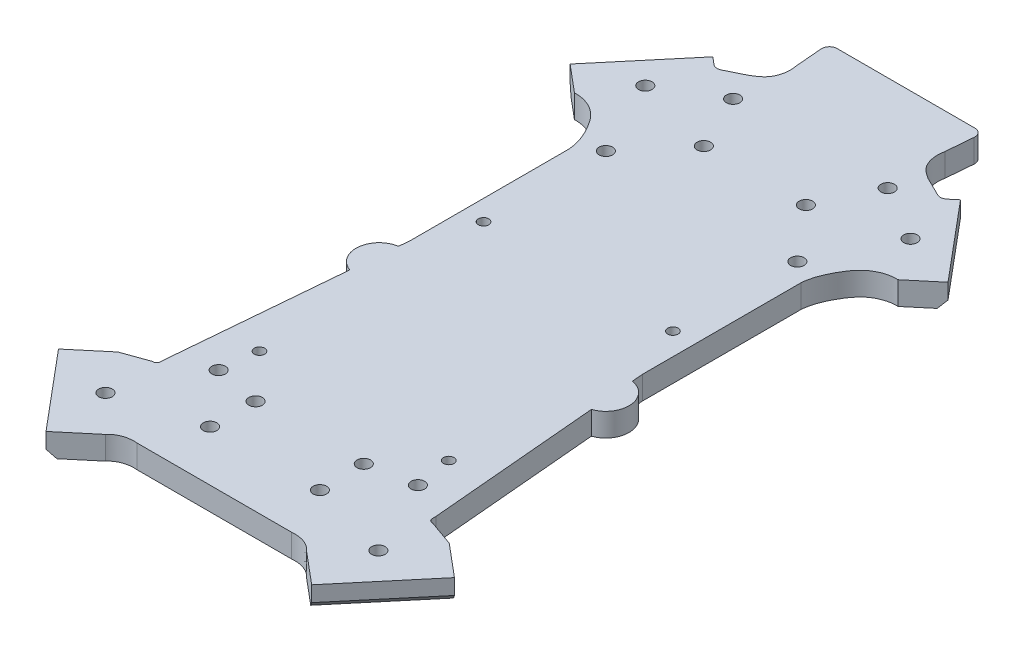
SolidWorks part; units mm, degrees
ref_plane "Front Plane" through (0, 0, 0) normal (0, 0, 1) x (1, 0, 0)
ref_plane "Top Plane" through (0, 0, 0) normal (0, 1, 0) x (1, 0, 0)
ref_plane "Right Plane" through (0, 0, 0) normal (1, 0, 0) x (0, 0, -1)
sketch "Sketch1" plane through (0, 0, 0) normal (0, 1, 0) x (1, 0, 0)
  line L1 (0, 0) -> (200, 0)
  line L2 (0, 0) -> (0, 200)
  line L3 (0, 200) -> (200, 200)
  line L4 (200, 0) -> (200, 200)
  dimension "D1" = 200
  dimension "D2" = 200
extrude "Boss-Extrude1" add sketch "Sketch1" along normal blind 6
sketch "Sketch2" plane through (0, 0, 0) normal (0, -1, 0) x (1, 0, 0)
  line L0 (143.2063, -38.4743) -> (139.3486, -82.5678)
  line L2 (138.3335, -94.1709) -> (138.0819, -97.0459)
  line L3 (138.0819, -97.0459) -> (138.0819, -138.1223)
  line L5 (128.0819, -16.2435) -> (88.0819, -16.2435)
  line L8 (72.9576, -38.4743) -> (76.8153, -82.5678)
  line L10 (77.8304, -94.1709) -> (78.0819, -97.0459)
  line L11 (78.0819, -97.0459) -> (78.0819, -138.1223)
  line L12 (136.0689, -175.4633) -> (131.2216, -177.8581)
  line L14 (127.295, -186.0703) -> (127.8892, -193.0744)
  line L15 (125.8964, -195.2435) -> (90.2675, -195.2435)
  line L16 (108.0819, -195.2435) -> (108.0819, -160.9159) construction
  line L17 (88.8688, -186.0703) -> (88.2746, -193.0744)
  line L18 (80.095, -175.4633) -> (84.9422, -177.8581)
  line L21 (71.8743, -36.5483) -> (65.2141, -34.1729)
  line L22 (65.2141, -34.1729) -> (56.8447, -27.1502)
  line L23 (56.8447, -27.1502) -> (73.7024, -7.0599)
  line L25 (73.7024, -7.0599) -> (82.0719, -14.0827)
  line L30 (66.2141, -151.3141) -> (63.7367, -153.3929)
  line L32 (63.7367, -153.3929) -> (59.1776, -157.2184)
  line L33 (59.1776, -157.2184) -> (76.0353, -177.3087)
  line L35 (76.0353, -177.3087) -> (77.9235, -175.7243)
  line L37 (142.4614, -7.0599) -> (134.092, -14.0827)
  line L38 (159.3191, -27.1502) -> (142.4614, -7.0599)
  line L39 (150.9497, -34.1729) -> (159.3191, -27.1502)
  line L40 (144.2896, -36.5483) -> (150.9497, -34.1729)
  line L45 (149.9497, -151.3141) -> (152.4271, -153.3929)
  line L46 (152.4271, -153.3929) -> (156.9863, -157.2184)
  line L47 (156.9863, -157.2184) -> (140.1285, -177.3087)
  line L48 (140.1285, -177.3087) -> (138.2403, -175.7243)
  line L49 (0, 0) -> (0, -200)
  line L50 (200, 0) -> (0, 0)
  line L51 (200, -200) -> (200, 0)
  line L52 (0, -200) -> (200, -200)
  arc A0 (138.3335, -94.1709) -> (139.3486, -82.5678) centre (137.4028, -88.2435) ccw
  arc A1 (76.8153, -82.5678) -> (77.8304, -94.1709) centre (78.761, -88.2435) ccw
  arc A2 (90.2675, -195.2435) -> (88.2746, -193.0744) centre (90.2675, -193.2435) cw
  arc A3 (127.8892, -193.0744) -> (125.8964, -195.2435) centre (125.8964, -193.2435) cw
  arc A4 (136.0689, -175.4633) -> (138.2403, -175.7243) centre (136.9547, -177.2564) cw
  arc A5 (80.095, -175.4633) -> (77.9235, -175.7243) centre (79.2091, -177.2564) ccw
  spline S2 degree 3 poles (131.2216, -177.8581) (130.2903, -178.4486) (127.4099, -180.2573) (126.8726, -184.0516) (127.295, -186.0703) knots 0 0 0 0 0.342841 1 1 1 1
  spline S3 degree 3 poles (84.9422, -177.8581) (85.8735, -178.4486) (88.754, -180.2573) (89.2912, -184.0516) (88.8688, -186.0703) knots 0 0 0 0 0.342841 1 1 1 1
  spline S6 degree 3 poles (134.092, -14.0827) (132.6324, -15.7971) (130.2548, -16.4555) (128.0819, -16.2435) knots 0 0 0 0 1 1 1 1
  spline S7 degree 3 poles (82.0719, -14.0827) (83.5315, -15.7971) (85.9091, -16.4555) (88.0819, -16.2435) knots 0 0 0 0 1 1 1 1
  spline S8 degree 3 poles (71.8743, -36.5483) (73.0299, -36.4607) (72.9809, -37.7548) (72.9576, -38.4743) knots 0 0 0 0 1 1 1 1
  spline S9 degree 3 poles (144.2896, -36.5483) (143.1339, -36.4607) (143.1829, -37.7548) (143.2063, -38.4743) knots 0 0 0 0 1 1 1 1
  spline S10 degree 3 poles (138.0819, -138.1223) (138.279, -140.6987) (139.8757, -144.4578) (142.8577, -148.8728) (146.318, -150.9496) (148.7119, -151.3752) (149.9497, -151.3141) knots 0 0 0 0 0.390118 0.632218 0.808161 1 1 1 1
  spline S11 degree 3 poles (78.0819, -138.1223) (77.8849, -140.6987) (76.2881, -144.4578) (73.3061, -148.8728) (69.8459, -150.9496) (67.4519, -151.3752) (66.2141, -151.3141) knots 0 0 0 0 0.390118 0.632218 0.808161 1 1 1 1
  point P39 (0, 0)
  point P59 (0, 0)
  point P60 (0, 0)
  point P72 (0, 0)
  point P90 (147.6197, -35.3606)
  point P104 (128.0733, -195.2435)
extrude "Cut-Extrude2" cut sketch "Sketch2" against normal through all both and the other way through all
hole_wizard "Ø3.0mm Dowel Hole1" positions "Sketch4" profile "Sketch5" hole size "Ø3.0" standard "ANSI Metric" end condition through all
sketch "Sketch4" plane through (0, 0, 0) normal (0, -1, 0) x (-1, 0, 0)
  point P0 (-83.2968, 142.3491)
  point P3 (-94.867, 156.1379)
  point P6 (-121.2968, 156.1379)
  point P9 (-132.867, 142.3491)
  point P12 (-128.0819, 170.5038)
  point P15 (-142.4028, 162.0993)
  point P18 (-88.0819, 170.5038)
  point P21 (-73.761, 162.0993)
  point P24 (-133.867, 43.1379)
  point P27 (-122.0819, 40.922)
  point P30 (-122.2968, 29.3491)
  point P33 (-94.0819, 40.922)
  point P36 (-93.867, 29.3491)
  point P39 (-82.2968, 43.1379)
  point P42 (-72.761, 23.3877)
  point P45 (-143.4028, 23.3877)
sketch "Sketch5" plane through (83.2968, 0, -142.3491) normal (1, 0, 0) x (0, 0, -1)
  line L0 (0, 0) -> (0, 6)
  line L1 (0, 6) -> (1.75, 6)
  line L2 (1.75, 6) -> (1.75, 0)
  line L5 (1.75, 0) -> (0, 0)
  line L11 (0, -6.35) -> (0, 107.95) construction
  dimension "Thru Hole Dia." = 3.5
  dimension "Thru Hole Depth" = 6
sketch "Sketch6" plane through (0, 0, 0) normal (0, -1, 0) x (1, 0, 0)
  line L0 (125.0968, -27.7325) -> (122.2968, -26.1159)
  line L1 (122.2968, -26.1159) -> (119.4968, -27.7325)
  line L2 (119.4968, -27.7325) -> (119.4968, -30.9657)
  line L5 (119.4968, -30.9657) -> (122.2968, -32.5823)
  line L6 (122.2968, -32.5823) -> (125.0968, -30.9657)
  line L7 (125.0968, -30.9657) -> (125.0968, -27.7325)
  line L8 (133.867, -39.9047) -> (131.067, -41.5213)
  line L9 (131.067, -41.5213) -> (131.067, -44.7545)
  line L10 (131.067, -44.7545) -> (133.867, -46.3711)
  line L11 (133.867, -46.3711) -> (136.667, -44.7545)
  line L12 (136.667, -44.7545) -> (136.667, -41.5213)
  line L13 (136.667, -41.5213) -> (133.867, -39.9047)
  line L22 (82.2968, -39.9047) -> (79.4968, -41.5213)
  line L23 (79.4968, -41.5213) -> (79.4968, -44.7545)
  line L24 (79.4968, -44.7545) -> (82.2968, -46.3711)
  line L26 (82.2968, -46.3711) -> (85.0968, -44.7545)
  line L27 (85.0968, -44.7545) -> (85.0968, -41.5213)
  line L30 (85.0968, -41.5213) -> (82.2968, -39.9047)
  line L31 (93.867, -26.1159) -> (91.067, -27.7325)
  line L34 (91.067, -27.7325) -> (91.067, -30.9657)
  line L36 (91.067, -30.9657) -> (93.867, -32.5823)
  line L37 (93.867, -32.5823) -> (96.667, -30.9657)
  line L38 (96.667, -30.9657) -> (96.667, -27.7325)
  line L39 (96.667, -27.7325) -> (93.867, -26.1159)
  line L40 (94.867, -152.9047) -> (92.067, -154.5213)
  line L41 (92.067, -154.5213) -> (92.067, -157.7545)
  line L42 (92.067, -157.7545) -> (94.867, -159.3711)
  line L43 (94.867, -159.3711) -> (97.667, -157.7545)
  line L44 (97.667, -157.7545) -> (97.667, -154.5213)
  line L45 (97.667, -154.5213) -> (94.867, -152.9047)
  line L46 (83.2968, -139.1159) -> (80.4968, -140.7325)
  line L47 (80.4968, -140.7325) -> (80.4968, -143.9657)
  line L48 (80.4968, -143.9657) -> (83.2968, -145.5823)
  line L49 (83.2968, -145.5823) -> (86.0968, -143.9657)
  line L50 (86.0968, -143.9657) -> (86.0968, -140.7325)
  line L51 (86.0968, -140.7325) -> (83.2968, -139.1159)
  line L52 (121.2968, -152.9047) -> (118.4968, -154.5213)
  line L53 (118.4968, -154.5213) -> (118.4968, -157.7545)
  line L54 (118.4968, -157.7545) -> (121.2968, -159.3711)
  line L55 (121.2968, -159.3711) -> (124.0968, -157.7545)
  line L56 (124.0968, -157.7545) -> (124.0968, -154.5213)
  line L57 (124.0968, -154.5213) -> (121.2968, -152.9047)
  line L58 (132.867, -145.5823) -> (135.667, -143.9657)
  line L59 (135.667, -143.9657) -> (135.667, -140.7325)
  line L60 (135.667, -140.7325) -> (132.867, -139.1159)
  line L61 (132.867, -139.1159) -> (130.067, -140.7325)
  line L62 (130.067, -140.7325) -> (130.067, -143.9657)
  line L63 (130.067, -143.9657) -> (132.867, -145.5823)
extrude "Cut-Extrude3" cut sketch "Sketch6" against normal blind 2.2
sketch "Sketch7" plane through (0, 0, 0) normal (0, -1, 0) x (-1, 0, 0)
  circle A0 centre (-83.3425, 52.6603) radius 1.35
  circle A1 centre (-132.3425, 52.6603) radius 1.35
  circle A2 centre (-83.3425, 110.6603) radius 1.35
  circle A3 centre (-132.3425, 110.6603) radius 1.35
extrude "Cut-Extrude4" cut sketch "Sketch7" along normal through all both and the other way through all
chamfer "Chamfer2" distance 2 angle 45 4 edges at (148.5574, 0, -167.2636) (67.6064, 0, -167.2636) (65.2736, 0, -17.105) (150.8903, 0, -17.105)
